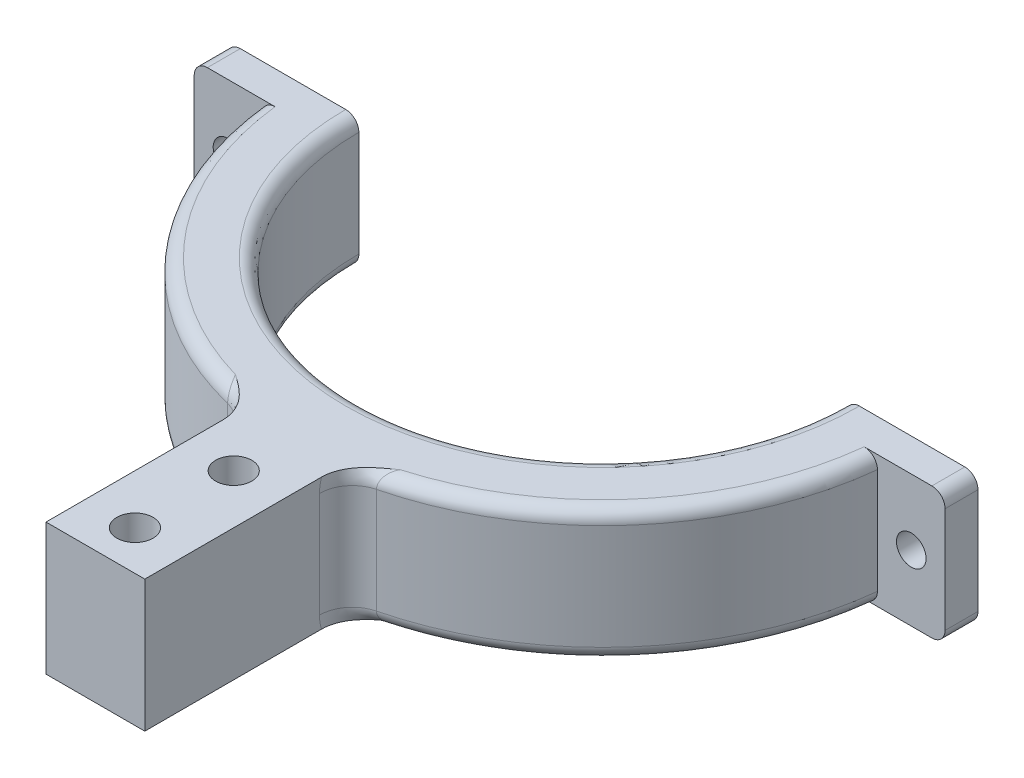
SolidWorks part; units mm, degrees
ref_plane "Front Plane" through (0, 0, 0) normal (0, 0, 1) x (1, 0, 0)
ref_plane "Top Plane" through (0, 0, 0) normal (0, 1, 0) x (1, 0, 0)
ref_plane "Right Plane" through (0, 0, 0) normal (1, 0, 0) x (0, 0, -1)
sketch "Sketch1" plane through (0, 0, 0) normal (0, 1, 0) x (1, 0, 0)
  line L0 (-37, 0) -> (37, 0) construction
  line L1 (-37, 0) -> (-57, 0)
  line L2 (-57, 0) -> (-57, -5)
  line L3 (-57, -5) -> (-46.7333, -5)
  line L4 (0, -47) -> (0, 68.2645) construction
  line L5 (57, -5) -> (46.7333, -5)
  line L6 (57, 0) -> (57, -5)
  line L7 (37, 0) -> (57, 0)
  arc A0 (-37, 0) -> (37, 0) centre (0, 0) ccw
  arc A1 (-46.7333, -5) -> (46.7333, -5) centre (0, 0) ccw
  circle A3 centre (0, 0) radius 47 construction
  circle A5 centre (0, 0) radius 37 construction
  point P12 (-47, 0)
  point P13 (47, 0)
  point P18 (35.3833, 10.8178)
  dimension "D1" = 74
  dimension "D3" = 5
  dimension "D4" = 10
  dimension "D2" = 10
extrude "Boss-Extrude1" add sketch "Sketch1" along normal blind 20
ref_plane "Plane1" through (0, 0, 47) normal (0, 0, 1) x (1, 0, 0)
sketch "Sketch2" plane through (0, 0, 47) normal (0, 0, 1) x (1, 0, 0)
  line L0 (0, 0) -> (0, 20) construction
  line L1 (46.7333, 20) -> (-46.7333, 20) construction
  line L3 (-7.5, 0) -> (7.5, 0)
  line L4 (-7.5, 0) -> (-7.5, 20)
  line L5 (-7.5, 20) -> (7.5, 20)
  line L6 (7.5, 0) -> (7.5, 20)
  line L7 (-7.5, 0) -> (7.5, 20) construction
  line L8 (-7.5, 20) -> (7.5, 0) construction
  point P5 (0, 10)
  dimension "D1" = 15
extrude "Boss-Extrude2" add sketch "Sketch2" along normal blind 30 and the other way up to surface other way up to face at (0, 10, 26)
sketch "Sketch3" plane through (0, 0, 5) normal (0, 0, 1) x (1, 0, 0)
  line L0 (-51.8666, 20) -> (-51.8666, 0) construction
  line L1 (-57, 20) -> (-46.7333, 20) construction
  line L2 (-57, 0) -> (-46.7333, 0) construction
  circle A0 centre (-51.8666, 10) radius 2.25
  dimension "D1" = 4.5
extrude "Cut-Extrude1" cut sketch "Sketch3" against normal through all
mirror "Mirror1" about plane through (0, 0, 0) normal (1, 0, 0) of "Cut-Extrude1"
sketch "Sketch4" plane through (0, 20, 0) normal (0, 1, 0) x (1, 0, 0)
  circle A0 centre (0, -56) radius 2.75
  circle A1 centre (0, -71) radius 2.75
  point P4 (0, -71)
  point P5 (0, -56)
  dimension "D1" = 5.5
  dimension "D2" = 5.5
extrude "Cut-Extrude2" cut sketch "Sketch4" against normal through all
fillet "Fillet1" radius 2 10 edges at (-57, 0, 2.5) (-57, 20, 2.5) (57, 0, 2.5) (57, 20, 2.5) (0, 20, 37) (0, 0, 37) (-34.1139, 0, 32.3302) (34.1139, 0, 32.3302) (34.1139, 20, 32.3302) (-34.1139, 20, 32.3302)
fillet "Fillet2" radius 5 6 edges at (-7.5, 19.5513, 45.6504) (-7.5, 0.7628, 45.9635) (7.5, 0.4487, 45.6504) (7.5, 19.2372, 45.9635) (-7.5, 10, 46.3977) (7.5, 10, 46.3977)
